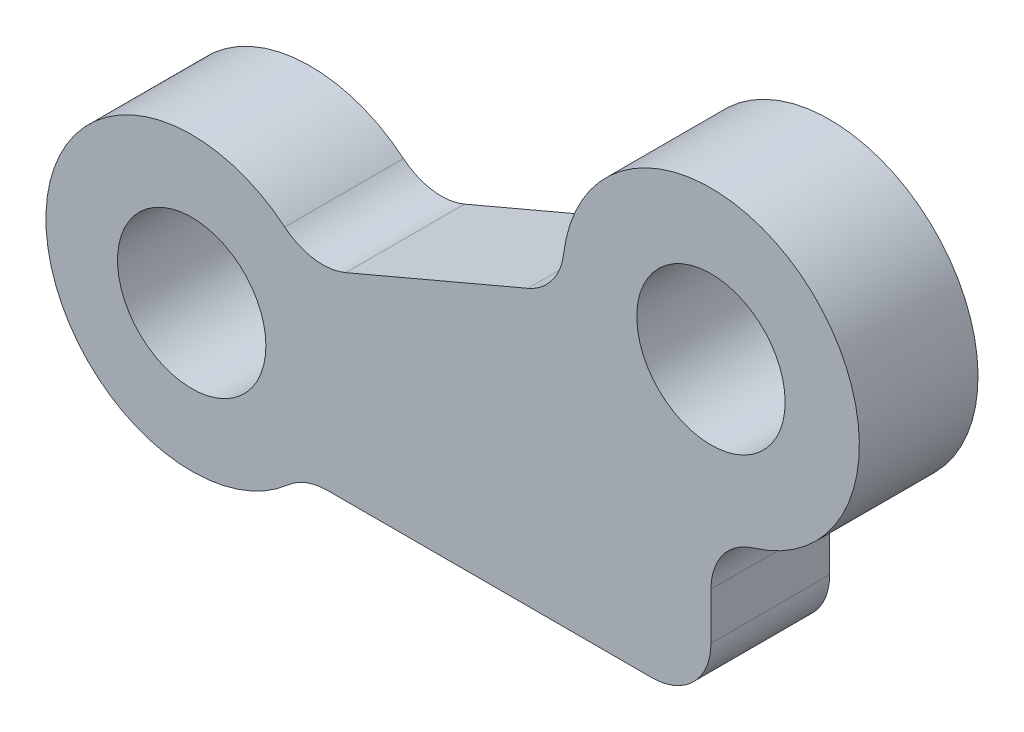
SolidWorks part; units mm, degrees
ref_plane "Front Plane" through (0, 0, 0) normal (0, 0, 1) x (1, 0, 0)
ref_plane "Top Plane" through (0, 0, 0) normal (0, 1, 0) x (1, 0, 0)
ref_plane "Right Plane" through (0, 0, 0) normal (1, 0, 0) x (0, 0, -1)
sketch "Sketch1" plane through (0, 0, 0) normal (0, 0, 1) x (1, 0, 0)
  line L0 (143.3333, 493) -> (716.6667, 493) construction
  line L1 (56.8391, 28.5799) -> (56.8391, 23.2923)
  line L2 (56.8391, 23.2923) -> (43.0826, 23.2923)
  line L3 (51.8645, 33.076) -> (43.2731, 29.4209)
  circle A2 centre (39.3406, 26.4759) radius 2.5
  circle A3 centre (56.8391, 33.5799) radius 2.5
  arc A4 (56.8391, 28.5799) -> (51.8645, 33.076) centre (56.8391, 33.5799) ccw
  arc A5 (43.2731, 29.4209) -> (43.0826, 23.2923) centre (39.3406, 26.4759) ccw
extrude "Boss-Extrude1" add sketch "Sketch1" along normal blind 4
fillet "Fillet1" radius 2 5 edges at (43.0826, 23.2923, 2) (56.8391, 23.2923, 2) (56.8391, 28.5799, 2) (43.2731, 29.4209, 2) (51.8645, 33.076, 2)
equation "\"D1@Fillet1\"=2"
